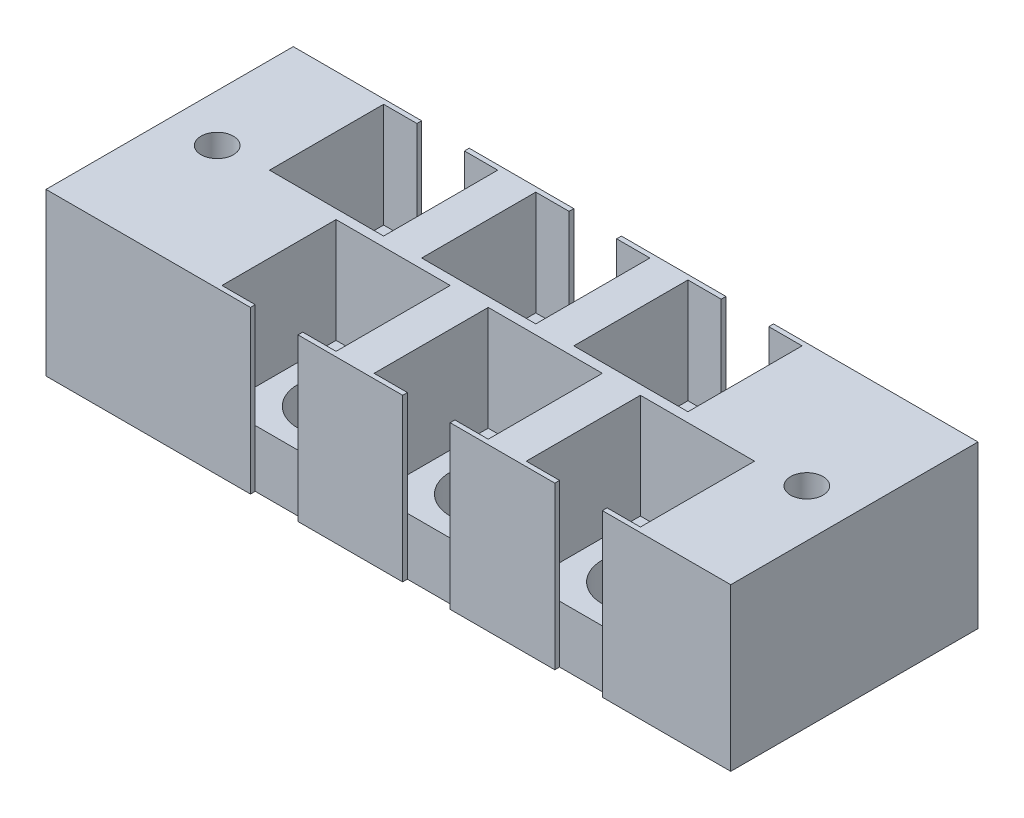
SolidWorks part; units mm, degrees
ref_plane "Front Plane" through (0, 0, 0) normal (0, 0, 1) x (1, 0, 0)
ref_plane "Top Plane" through (0, 0, 0) normal (0, 1, 0) x (1, 0, 0)
ref_plane "Right Plane" through (0, 0, 0) normal (1, 0, 0) x (0, 0, -1)
sketch "Sketch1" plane through (0, 0, 0) normal (0, 1, 0) x (1, 0, 0)
  line L0 (3.1864, -4.1649) -> (6.1864, -4.1649)
  line L1 (19.1864, -4.1649) -> (22.1864, -4.1649)
  line L2 (27.1864, -30.1649) -> (30.1864, -30.1649)
  line L3 (11.1864, -30.1649) -> (14.1864, -30.1649)
  line L4 (43.1864, -30.1649) -> (52.6864, -30.1649)
  line L5 (52.6864, -30.1649) -> (52.6864, -4.1649)
  line L6 (52.6864, -4.1649) -> (35.1864, -4.1649)
  line L7 (-9.8136, -4.1649) -> (-19.3136, -4.1649)
  line L8 (-19.3136, -4.1649) -> (-19.3136, -30.1649)
  line L9 (-19.3136, -30.1649) -> (-1.8136, -30.1649)
  line L10 (-14.3136, -4.1649) -> (-14.3136, -30.1649) construction
  line L11 (47.6864, -4.1649) -> (47.6864, -30.1649) construction
  circle A0 centre (-14.3136, -17.1649) radius 1.7
  circle A1 centre (47.6864, -17.1649) radius 1.7
  line B0 (35.1864, -17.1649) -> (35.1864, -4.1649)
  line B1 (11.1864, -30.1649) -> (7.1864, -30.1649)
  line B2 (-1.3136, -29.6649) -> (10.6864, -29.6649)
  line B3 (11.1864, -30.1649) -> (11.1864, -17.1649)
  line B4 (27.1864, -30.1649) -> (27.1864, -17.1649)
  line B5 (43.1864, -30.1649) -> (43.1864, -17.1649)
  line B6 (-1.8136, -17.1649) -> (-1.8136, -30.1649)
  line B7 (10.6864, -29.6649) -> (10.6864, -17.6649)
  line B8 (30.1864, -17.1649) -> (30.1864, -30.1649)
  line B9 (22.1864, -4.1649) -> (22.1864, -17.1649)
  line B10 (34.6864, -16.6649) -> (34.6864, -4.6649)
  line B11 (18.6864, -16.6649) -> (18.6864, -4.6649)
  line B12 (3.1864, -17.1649) -> (3.1864, -4.1649)
  line B13 (42.6864, -29.6649) -> (42.6864, -17.6649)
  line B14 (14.6864, -29.6649) -> (26.6864, -29.6649)
  line B15 (30.6864, -17.6649) -> (30.6864, -29.6649)
  line B16 (30.6864, -17.6649) -> (42.6864, -29.6649) construction
  line B17 (14.6864, -17.6649) -> (26.6864, -29.6649) construction
  line B18 (-1.3136, -17.6649) -> (10.6864, -29.6649) construction
  line B19 (43.1864, -17.1649) -> (30.1864, -17.1649)
  line B20 (2.6864, -16.6649) -> (2.6864, -4.6649)
  line B21 (14.6864, -17.6649) -> (14.6864, -29.6649)
  line B22 (27.1864, -30.1649) -> (23.1864, -30.1649)
  line B23 (30.1864, -30.1649) -> (34.1864, -30.1649)
  line B24 (43.1864, -30.1649) -> (39.1864, -30.1649)
  line B25 (-9.3136, -10.6649) -> (2.6864, -10.6649) construction
  line B26 (6.6864, -10.6649) -> (18.6864, -10.6649) construction
  line B27 (22.6864, -10.6649) -> (34.6864, -10.6649) construction
  line B28 (-1.3136, -23.6649) -> (10.6864, -23.6649) construction
  line B29 (14.6864, -23.6649) -> (26.6864, -23.6649) construction
  line B30 (30.6864, -23.6649) -> (42.6864, -23.6649) construction
  line B31 (-27.4152, -23.6649) -> (51.2342, -23.6649) construction
  line B32 (22.1864, -17.1649) -> (35.1864, -17.1649)
  line B33 (-27.4152, -10.6649) -> (51.2342, -10.6649) construction
  line B34 (28.6864, -16.6649) -> (28.6864, -4.6649) construction
  line B35 (36.6864, -17.6649) -> (36.6864, -29.6649) construction
  line B36 (20.6864, -17.6649) -> (20.6864, -29.6649) construction
  line B37 (12.6864, -16.6649) -> (12.6864, -4.6649) construction
  line B38 (4.6864, -17.6649) -> (4.6864, -29.6649) construction
  line B39 (-3.3136, -16.6649) -> (-3.3136, -4.6649) construction
  line B40 (22.6864, -4.6649) -> (22.6864, -16.6649)
  line B41 (22.6864, -16.6649) -> (34.6864, -16.6649)
  line B42 (34.6864, -4.6649) -> (22.6864, -4.6649)
  line B43 (34.6864, -16.6649) -> (22.6864, -4.6649) construction
  line B44 (34.6864, -4.6649) -> (22.6864, -16.6649) construction
  line B45 (35.1864, -4.1649) -> (31.1864, -4.1649)
  line B46 (22.1864, -4.1649) -> (26.1864, -4.1649)
  line B47 (31.1864, -4.1649) -> (31.1864, -4.6649)
  line B48 (26.1864, -4.1649) -> (26.1864, -4.6649)
  circle B49 centre (28.6864, -10.6649) radius 4
  line B50 (-1.3136, -17.6649) -> (-1.3136, -29.6649)
  line B51 (10.6864, -17.6649) -> (-1.3136, -17.6649)
  line B52 (-1.3136, -29.6649) -> (10.6864, -17.6649) construction
  line B53 (11.1864, -17.1649) -> (-1.8136, -17.1649)
  line B54 (-1.8136, -30.1649) -> (2.1864, -30.1649)
  line B55 (2.1864, -30.1649) -> (2.1864, -29.6649)
  line B56 (7.1864, -30.1649) -> (7.1864, -29.6649)
  circle B57 centre (4.6864, -23.6649) radius 4
  line B58 (26.6864, -29.6649) -> (26.6864, -17.6649)
  line B59 (26.6864, -17.6649) -> (14.6864, -17.6649)
  line B60 (14.6864, -29.6649) -> (26.6864, -17.6649) construction
  line B61 (27.1864, -17.1649) -> (14.1864, -17.1649)
  line B62 (14.1864, -17.1649) -> (14.1864, -30.1649)
  line B63 (14.1864, -30.1649) -> (18.1864, -30.1649)
  line B64 (18.1864, -30.1649) -> (18.1864, -29.6649)
  line B65 (23.1864, -30.1649) -> (23.1864, -29.6649)
  circle B66 centre (20.6864, -23.6649) radius 4
  line B67 (42.6864, -17.6649) -> (30.6864, -17.6649)
  line B68 (30.6864, -29.6649) -> (42.6864, -29.6649)
  line B69 (30.6864, -29.6649) -> (42.6864, -17.6649) construction
  line B70 (34.1864, -30.1649) -> (34.1864, -29.6649)
  line B71 (39.1864, -30.1649) -> (39.1864, -29.6649)
  circle B72 centre (36.6864, -23.6649) radius 4
  line B73 (6.6864, -4.6649) -> (6.6864, -16.6649)
  line B74 (6.6864, -16.6649) -> (18.6864, -16.6649)
  line B75 (18.6864, -4.6649) -> (6.6864, -4.6649)
  line B76 (18.6864, -16.6649) -> (6.6864, -4.6649) construction
  line B77 (18.6864, -4.6649) -> (6.6864, -16.6649) construction
  line B78 (6.1864, -17.1649) -> (19.1864, -17.1649)
  line B79 (19.1864, -17.1649) -> (19.1864, -4.1649)
  line B80 (6.1864, -4.1649) -> (6.1864, -17.1649)
  line B81 (19.1864, -4.1649) -> (15.1864, -4.1649)
  line B82 (6.1864, -4.1649) -> (10.1864, -4.1649)
  line B83 (15.1864, -4.1649) -> (15.1864, -4.6649)
  line B84 (10.1864, -4.1649) -> (10.1864, -4.6649)
  circle B85 centre (12.6864, -10.6649) radius 4
  line B86 (-9.3136, -4.6649) -> (-9.3136, -16.6649)
  line B87 (-9.3136, -16.6649) -> (2.6864, -16.6649)
  line B88 (2.6864, -4.6649) -> (-9.3136, -4.6649)
  line B89 (2.6864, -16.6649) -> (-9.3136, -4.6649) construction
  line B90 (2.6864, -4.6649) -> (-9.3136, -16.6649) construction
  line B91 (-9.8136, -17.1649) -> (3.1864, -17.1649)
  line B92 (-9.8136, -4.1649) -> (-9.8136, -17.1649)
  line B93 (3.1864, -4.1649) -> (-0.8136, -4.1649)
  line B94 (-9.8136, -4.1649) -> (-5.8136, -4.1649)
  line B95 (-0.8136, -4.1649) -> (-0.8136, -4.6649)
  line B96 (-5.8136, -4.1649) -> (-5.8136, -4.6649)
  circle B97 centre (-3.3136, -10.6649) radius 4
  dimension "D1" = 9.5
  dimension "D2" = 9.5
  dimension "D3" = 72
  dimension "D4" = 5
  dimension "D5" = 5
sketch_block_instance "Block1-5"
sketch_block "Block1" parameters "D3"=6, "D1"=12, "D2"=12, "D4"=12, "D5"=78.6494, "D6"=78.6494, "D7"=78.6494, "D8"=10.3235, "D9"=14.0261, "D10"=17.7654, "D11"=23.7534, "D12"=22.7743, "D13"=52
sketch_block_instance "Block2-2"
sketch_block "Block2" parameters "D1"=12
sketch_block_instance "Block2-3"
sketch_block_instance "Block2-4"
sketch_block_instance "Block2-5"
sketch_block_instance "Block2-6"
sketch_block_instance "Block2-7"
sketch_block_instance "Block3-1"
sketch_block "Block3"
sketch_block_instance "Block4-1"
sketch_block "Block4"
sketch_block_instance "Block5-1"
sketch_block "Block5"
sketch_block_instance "Block6-1"
sketch_block "Block6"
sketch_block_instance "Block7-1"
sketch_block "Block7"
sketch_block_instance "Block8-1"
sketch_block "Block8"
extrude "Boss-Extrude1" add sketch "Sketch1" along normal blind 6 contours B20 B88 B86 B87 B97 | B11 B75 B73 B74 B85 | B10 B42 B40 B41 B49 | B21 B14 B58 B59 B66 | B50 B2 B7 B51 B57 | B15 B68 B13 B67 B72 region at (0.9364, 0, 4.8346) region at (12.6864, 0, 4.8346) region at (0.4364, 0, 29.4952) region at (16.4364, 0, 29.4952) region at (28.6864, 0, 4.8346) region at (32.4364, 0, 29.4952)
extrude "Boss-Extrude2" add sketch "Sketch1<3>" along normal blind 17 contours B5 L4 L5 L6 B0 B19 A1 | B92 L7 L8 L9 B6 B91 A0 | B12 B53 B80 L0 | B78 B3 L3 B62 | B8 B32 B4 L2 | B71 B24 B5 B19 B32 B8 B23 B70 B68 B15 B67 B13 | B65 B22 B4 B32 B61 B62 B63 B64 B14 B21 B59 B58 | B96 B94 B92 B91 B53 B12 B93 B95 B88 B20 B87 B86 | B84 B82 B80 B53 B78 B61 B79 B81 B83 B75 B11 B74 B73 | B79 B61 B9 L1 | B48 B46 B9 B32 B0 B45 B47 B42 B10 B41 B40 | B56 B1 B3 B53 B6 B54 B55 B2 B50 B51 B7 region at (4.6864, 0, 10.6649) region at (3.0025, 0, 10.6649) region at (8.1864, 0, 4.3487) region at (4.6864, 0, 17.3487) region at (-11.9088, 0, 19.1419) region at (12.6864, 0, 23.6649) region at (16.6864, 0, 17.3487) region at (20.6864, 0, 10.6649) region at (22.3702, 0, 10.6649) region at (28.6864, 0, 23.6649) region at (32.6864, 0, 17.3487) region at (45.2816, 0, 15.1878)
sketch "Sketch1<3>" plane through (0, 0, 0) normal (0, 1, 0) x (1, 0, 0) same geometry as "Sketch1"
sketch "Sketch2" plane through (0, 0, 0) normal (0, -1, 0) x (1, 0, 0)
  line L0 (3.1864, 4.1649) -> (-0.8136, 4.1649) construction
  line L4 (26.1864, 4.1649) -> (15.1864, 4.1649) construction
  line L7 (26.1864, 4.1649) -> (26.1864, 4.6649) construction
  line L8 (35.1864, 4.1649) -> (31.1864, 4.1649) construction
  point P2 (1.1864, 4.1649)
  point P11 (20.6864, 4.1649)
  point P18 (26.1864, 4.4149)
  point P21 (33.1864, 4.1649)
  line B0 (1.3864, 19.6649) -> (1.3864, 14.6649)
  line B1 (1.3864, 14.6649) -> (-0.8136, 14.6649)
  line B2 (-0.8136, 14.6649) -> (-0.8136, 19.6649)
  line B3 (-0.8136, 19.6649) -> (1.3864, 19.6649)
  line B4 (10.1864, 19.6649) -> (10.1864, 14.6649)
  line B5 (10.1864, 14.6649) -> (7.9864, 14.6649)
  line B6 (7.9864, 14.6649) -> (7.9864, 19.6649)
  line B7 (7.9864, 19.6649) -> (10.1864, 19.6649)
  line B8 (17.3864, 19.6649) -> (17.3864, 14.6649)
  line B9 (17.3864, 14.6649) -> (15.1864, 14.6649)
  line B10 (15.1864, 14.6649) -> (15.1864, 19.6649)
  line B11 (15.1864, 19.6649) -> (17.3864, 19.6649)
  line B12 (26.1864, 19.6649) -> (26.1864, 14.6649)
  line B13 (26.1864, 14.6649) -> (23.9864, 14.6649)
  line B14 (23.9864, 14.6649) -> (23.9864, 19.6649)
  line B15 (23.9864, 19.6649) -> (26.1864, 19.6649)
  line B16 (33.3864, 19.6649) -> (33.3864, 14.6649)
  line B17 (33.3864, 14.6649) -> (31.1864, 14.6649)
  line B18 (31.1864, 14.6649) -> (31.1864, 19.6649)
  line B19 (31.1864, 19.6649) -> (33.3864, 19.6649)
sketch_block_instance "Block9-4"
sketch_block "Block9"
sketch_block_instance "Block9-5"
sketch_block_instance "Block9-6"
sketch_block_instance "Block9-7"
sketch_block_instance "Block9-8"
extrude "Boss-Extrude3" add sketch "Sketch2" along normal blind 7
sketch "Sketch3" plane through (0, 0, 0) normal (0, -1, 0) x (1, 0, 0)
  text T0 "F6"
extrude "Cut-Extrude1" cut sketch "Sketch3" against normal blind 1
